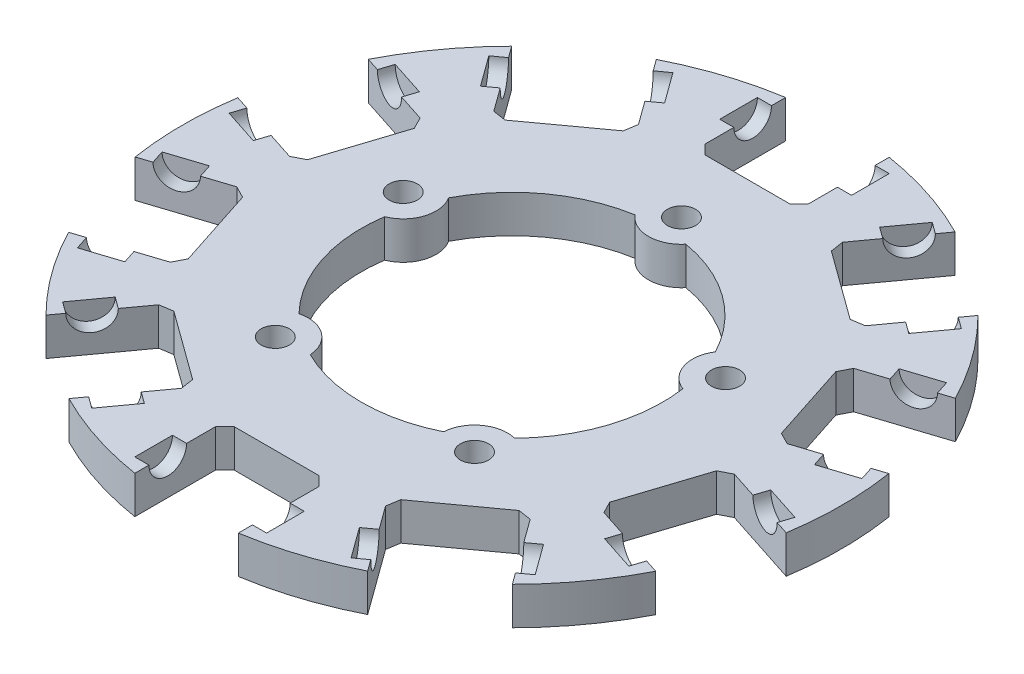
SolidWorks part; units mm, degrees
ref_plane "Ebene vorne" through (0, 0, 0) normal (0, 0, 1) x (1, 0, 0)
ref_plane "Ebene oben" through (0, 0, 0) normal (0, 1, 0) x (1, 0, 0)
ref_plane "Ebene rechts" through (0, 0, 0) normal (1, 0, 0) x (0, 0, -1)
sketch "Skizze1" plane through (0, 0, 0) normal (0, 1, 0) x (1, 0, 0)
  circle A0 centre (0, 0) radius 35
  dimension "D1" = 70
extrude "Aufsatz-Linear austragen1" add sketch "Skizze1" along normal blind 4
ref_axis "Achse2" through (0, 4, 0) along (0, -1, 0)
sketch "Skizze2" plane through (0, 4, 0) normal (0, 1, 0) x (1, 0, 0)
  line L0 (0, 0) -> (0, 35) construction
  line L1 (5.5, 0) -> (5.5, 37) construction
  line L2 (-5.5, 0) -> (-5.5, 37) construction
  line L3 (-5.5, 0) -> (-5.5, 35) construction
  line L4 (5.5, 0) -> (5.5, 35) construction
  line L5 (-5.5, 0) -> (0, 0) construction
  line L6 (0, 0) -> (5.5, 0) construction
  line L7 (-5.5, 37) -> (-5.5, 26)
  line L8 (-4.5, 25) -> (0, 25)
  line L9 (0, 25) -> (4.5, 25)
  line L10 (5.5, 26) -> (5.5, 37)
  line L11 (-5.5, 37) -> (5.5, 37)
  line L12 (4.5, 25) -> (5.5, 26)
  line L13 (-5.5, 26) -> (-4.5, 25)
  circle A0 centre (0, 0) radius 35 construction
  point P13 (-5.5, 25)
  point P17 (5.5, 25)
  dimension "D3" = 10
  dimension "D4" = 12
  dimension "D1" = 5.5
  dimension "D2" = 5.5
extrude "Schnitt-Linear austragen1" cut sketch "Skizze2" against normal through all
sketch "Skizze4" plane through (0, 4, 0) normal (0, 1, 0) x (1, 0, 0)
  line L0 (-7, 31.0652) -> (7, 31.0652)
  line L1 (-4.5, 25) -> (4.5, 25) construction
  line L2 (-7, 31.0652) -> (-7, 29.0652)
  line L3 (-7, 29.0652) -> (7, 29.0652)
  line L4 (7, 29.0652) -> (7, 31.0652)
  point P2 (0, 31.0652)
  point P5 (0, 25)
  dimension "D1" = 3.5
  dimension "D2" = 2
  dimension "D3" = 14
revolve "Schnitt-Rotation1" cut sketch "Skizze4" angle 360 about L0
pattern_circular "Kreismuster1" count 10 every 36 about axis through (0, 4, 0) along (0, -1, 0) of "Schnitt-Linear austragen1", "Schnitt-Rotation1"
sketch "Skizze5" plane through (0, 4, 0) normal (0, 1, 0) x (1, 0, 0)
  circle A0 centre (0, 0) radius 16
  dimension "D1" = 32
extrude "Schnitt-Linear austragen2" cut sketch "Skizze5" against normal through all
sketch "Skizze7" plane through (0, 0, 0) normal (0, -1, 0) x (-1, 0, 0)
  circle A0 centre (0, 18) radius 3.5
  dimension "D2" = 7
  dimension "D1" = 18
extrude "Aufsatz-Linear austragen2" add sketch "Skizze7" against normal up to surface (4 mm away) up to face at (0, 4, 16)
sketch "Skizze6" plane through (0, 0, 0) normal (0, -1, 0) x (1, 0, 0)
  line L0 (0, -25) -> (0, 0) construction
  line L1 (-4.5, -25) -> (4.5, -25) construction
  circle A0 centre (0, -18) radius 1.5
  dimension "D2" = 3
  dimension "D1" = 18
extrude "Schnitt-Linear austragen3" cut sketch "Skizze6" against normal through all
pattern_circular "Kreismuster2" count 5 every 72 about axis through (0, 4, 0) along (0, -1, 0) of "Schnitt-Linear austragen3", "Aufsatz-Linear austragen2"
